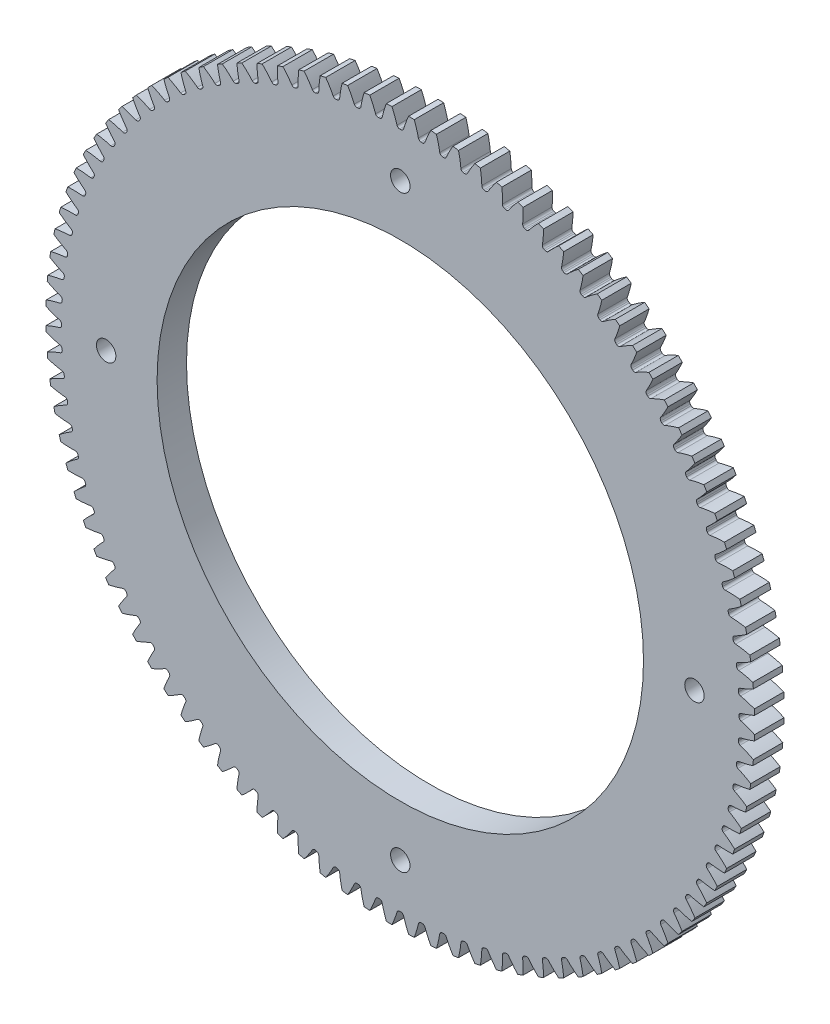
SolidWorks part; units mm, degrees
ref_plane "Front Plane" through (0, 0, 0) normal (0, 0, 1) x (1, 0, 0)
ref_plane "Top Plane" through (0, 0, 0) normal (0, 1, 0) x (1, 0, 0)
ref_plane "Right Plane" through (0, 0, 0) normal (1, 0, 0) x (0, 0, -1)
sketch "Sketch1" plane through (0, 0, 0) normal (0, 0, 1) x (1, 0, 0)
  line L0 (0, 0) -> (0, 75) construction
  line L1 (-24.1045, 83.7733) -> (24.1045, 66.2267) construction
  circle A0 centre (0, 0) radius 73.125 construction
  circle A1 centre (0, 0) radius 76.5 construction
  circle A2 centre (0, 0) radius 75 construction
  circle A3 centre (0, 0) radius 70.4769 construction
  circle A4 centre (0, 0) radius 40 construction
  circle A5 centre (0, 0) radius 7.5 construction
  point P8 (0.75, 0)
  point P13 (50, 0)
  dimension "OD" = 153
  dimension "Root Diameter" = 146.25
  dimension "Gear Pitch Diameter" = 150
  dimension "Base Diameter" = 140.9539
  dimension "Hub Diameter" = 80
  dimension "For Shaft Diameter" = 15
  dimension "Pressure Angle" = 20
  dimension "Number of Teeth" = 100
  dimension "Module" = 1.5
sketch "Sketch2" plane through (0, 0, 0) normal (1, 0, 0) x (0, 0, -1)
  line L0 (-14, 0) -> (6.35, 0) construction
  line L1 (6.35, 76.5) -> (6.35, -76.5) construction
  line L2 (0, -40) -> (-14, -40) construction
  line L3 (-14, 76.5) -> (6.35, 76.5) construction
  line L8 (-14, -40) -> (-14, 40) construction
  point P4 (0, 76.5)
  point P5 (-7, 0)
  dimension "Overall Width" = 20.35
  dimension "Hub Width" = 14
  dimension "Approx Set Screw Positon" = 7
  dimension "Face Width" = 6.35
sketch "Sketch3" plane through (0, 0, 0) normal (0, 0, 1) x (1, 0, 0)
  circle A0 centre (0, 0) radius 76.5
  circle A1 centre (0, 0) radius 76.5 construction
extrude "Boss-Extrude1" add sketch "Sketch3" against normal up to vertex (6.35 mm away) up to point (0, 0, -6.35)
sketch "Sketch4" plane through (0, 0, 0) normal (0, 0, 1) x (1, 0, 0)
  line L0 (73.1226, 0.589) -> (73.1226, -0.589)
  arc A3 (76.4789, 1.7978) -> (76.4789, -1.7978) centre (0, 0) cw
  circle A4 centre (0, 0) radius 76.5 construction
  arc A5 (73.1226, 0.589) -> (76.4789, 1.7978) centre (66.9977, 22.8603) ccw
  circle A8 centre (0, 0) radius 73.125 construction
  arc A9 (73.1226, -0.589) -> (76.4789, -1.7978) centre (66.9977, -22.8603) cw
  spline S0 degree 4 poles (70.4769, 0.0566) (70.4862, 0.0567) (70.5123, 0.0572) (70.5615, 0.0592) (70.6419, 0.0639) (70.7443, 0.072) (70.8767, 0.0848) (71.0327, 0.1031) (71.2042, 0.1265) (71.3909, 0.1556) (71.5772, 0.1877) (71.763, 0.2226) (71.9483, 0.2601) (72.1727, 0.3086) (72.4418, 0.3712) (72.7566, 0.4506) (73.1136, 0.5483) (73.4778, 0.6559) (73.8362, 0.7684) (74.1986, 0.8897) (74.5493, 1.0125) (74.9138, 1.148) (75.2504, 1.277) (75.6277, 1.4303) (75.9323, 1.5566) (76.3344, 1.7325) (76.572, 1.8392) (76.8501, 1.9673) (76.9736, 2.0258) (77.0497, 2.0619) knots 0 0 0 0 0 0.005377 0.015084 0.028532 0.04661 0.064855 0.092111 0.119476 0.146842 0.174209 0.201575 0.228941 0.256307 0.307035 0.361767 0.4165 0.471232 0.525964 0.580697 0.635429 0.690161 0.744894 0.799626 0.854358 0.909091 0.954545 1 1 1 1 1 construction
  spline S1 degree 4 poles (70.4769, 0.0566) (70.4862, 0.0567) (70.5123, 0.0572) (70.5615, 0.0592) (70.6419, 0.0639) (70.7443, 0.072) (70.8767, 0.0848) (71.0327, 0.1031) (71.2042, 0.1265) (71.3909, 0.1556) (71.5772, 0.1877) (71.763, 0.2226) (71.9483, 0.2601) (72.1727, 0.3086) (72.4418, 0.3712) (72.7566, 0.4506) (73.1136, 0.5483) (73.4778, 0.6559) (73.8362, 0.7684) (74.1986, 0.8897) (74.5493, 1.0125) (74.9138, 1.148) (75.2504, 1.277) (75.6277, 1.4303) (75.9323, 1.5566) (76.2472, 1.6943) (76.4005, 1.7625) (76.4789, 1.7978) knots 0 0 0 0 0 0.005377 0.015084 0.028532 0.04661 0.064855 0.092111 0.119476 0.146842 0.174209 0.201575 0.228941 0.256307 0.307035 0.361767 0.4165 0.471232 0.525964 0.580697 0.635429 0.690161 0.744894 0.799626 0.854358 0.909091 0.909091 0.909091 0.909091 0.909091 construction
  spline S2 degree 4 poles (70.4769, -0.0566) (70.4862, -0.0567) (70.5123, -0.0572) (70.5615, -0.0592) (70.6419, -0.0639) (70.7443, -0.072) (70.8767, -0.0848) (71.0327, -0.1031) (71.2042, -0.1265) (71.3909, -0.1556) (71.5772, -0.1877) (71.763, -0.2226) (71.9483, -0.2601) (72.1727, -0.3086) (72.4418, -0.3712) (72.7566, -0.4506) (73.1136, -0.5483) (73.4778, -0.6559) (73.8362, -0.7684) (74.1986, -0.8897) (74.5493, -1.0125) (74.9138, -1.148) (75.2504, -1.277) (75.6277, -1.4303) (75.9323, -1.5566) (76.3344, -1.7325) (76.572, -1.8392) (76.8501, -1.9673) (76.9736, -2.0258) (77.0497, -2.0619) knots 0 0 0 0 0 0.005377 0.015084 0.028532 0.04661 0.064855 0.092111 0.119476 0.146842 0.174209 0.201575 0.228941 0.256307 0.307035 0.361767 0.4165 0.471232 0.525964 0.580697 0.635429 0.690161 0.744894 0.799626 0.854358 0.909091 0.954545 1 1 1 1 1 construction
  spline S3 degree 4 poles (70.4769, -0.0566) (70.4862, -0.0567) (70.5123, -0.0572) (70.5615, -0.0592) (70.6419, -0.0639) (70.7443, -0.072) (70.8767, -0.0848) (71.0327, -0.1031) (71.2042, -0.1265) (71.3909, -0.1556) (71.5772, -0.1877) (71.763, -0.2226) (71.9483, -0.2601) (72.1727, -0.3086) (72.4418, -0.3712) (72.7566, -0.4506) (73.1136, -0.5483) (73.4778, -0.6559) (73.8362, -0.7684) (74.1986, -0.8897) (74.5493, -1.0125) (74.9138, -1.148) (75.2504, -1.277) (75.6277, -1.4303) (75.9323, -1.5566) (76.2472, -1.6943) (76.4005, -1.7625) (76.4789, -1.7978) knots 0 0 0 0 0 0.005377 0.015084 0.028532 0.04661 0.064855 0.092111 0.119476 0.146842 0.174209 0.201575 0.228941 0.256307 0.307035 0.361767 0.4165 0.471232 0.525964 0.580697 0.635429 0.690161 0.744894 0.799626 0.854358 0.909091 0.909091 0.909091 0.909091 0.909091 construction
  dimension "D1" = 1.1781
extrude "Cut-Extrude1" cut sketch "Sketch4" against normal through all both and the other way through all
fillet "Fillet1" radius 0.589 2 edges at (73.1226, 0.589, -3.175) (73.1226, -0.589, -3.175)
pattern_circular "CirPattern1" count 100 over 360 about axis through (0, 0, 14) along (0, 0, -1) of "Cut-Extrude1", "Fillet1"
sketch "Sketch5" plane through (0, 0, -6.35) normal (0, 0, -1) x (-1, 0, 0)
  circle A0 centre (0, 0) radius 52.5
  dimension "D1" = 105
extrude "Cut-Extrude2" cut sketch "Sketch5" against normal through all
sketch "Sketch6" plane through (0, 0, -6.35) normal (0, 0, -1) x (-1, 0, 0)
  circle A0 centre (63.5, 0) radius 2.1
  circle A1 centre (0, -63.5) radius 2.1
  circle A2 centre (-63.5, 0) radius 2.1
  circle A3 centre (0, 63.5) radius 2.1
  point P11 (0, 0)
  dimension "D1" = 4.2
  dimension "D3" = 127
  dimension "D2" = 4
extrude "Cut-Extrude3" cut sketch "Sketch6" against normal through all
sketch "Sketch7" plane through (0, 0, 0) normal (0, 0, 1) x (1, 0, 0)
  circle A0 centre (0, 0) radius 75 construction
  dimension "D1" = 150
sketch "Sketch8" plane through (0, 0, 0) normal (0, 1, 0) x (1, 0, 0)
  line L0 (0, 0) -> (0, 8.1709) construction
  line L1 (-75, 0) -> (75, 0) construction
equation "\"Number of Teeth\"= 100"
equation "\"Module\"= 1.5"
equation "\"Diametral Pitch\"= 1 / \"Module\""
equation "\"Dedendum\"= 1.25 / \"Diametral Pitch\""
equation "\"Pitch Diameter\"= \"Module\" * \"Number of Teeth\""
equation "\"Root Diameter\"= \"Pitch Diameter\" - ( 2 * \"Dedendum\" )"
equation "\"Root Diameter@Sketch1\"=\"Root Diameter\""
equation "\"OD@Sketch1\" = \"Outside Diameter\""
equation "\"D1@CirPattern1\"=\"Number of Teeth\""
equation "\"Pressure Angle\"=20"
equation "\"Base Diameter\"= \"Pitch Diameter\" * cos ( \"Pressure Angle\" )"
equation "\"Outside Diameter\"= ( \"Number of Teeth\" + 2 ) / \"Diametral Pitch\""
equation "\"Pitch Angle\"= 360deg / \"Number of Teeth\""
equation "\"Alpha\"= sqr ( \"Pitch Diameter\" ^ 2 - \"Base Diameter\" ^ 2 ) / \"Base Diameter\" * 180 / PI - \"Pressure Angle\""
equation "\"Beta\"= ( \"Pitch Angle\" / 4 - \"Alpha\" )"
equation "\"Phi\"= sqr ( ( \"Outside Diameter\" / 2 ) ^ 2 - ( \"Base Diameter\" / 2 ) ^ 2 ) / ( \"Base Diameter\" / 2 )"
equation "\"Addendum\"= 1 / \"Diametral Pitch\""
equation "\"WorkingDepth\"= 2 / \"Diametral Pitch\""
equation "\"WholeDepth\"= 2.25 / \"Diametral Pitch\""
equation "\"Clearance\"= 0.25 / \"Diametral Pitch\""
equation "\"ToothThickness\"= ( pi * 2 ) / \"Diametral Pitch\""
equation "\"CircularPitch\"= pi / \"Diametral Pitch\""
equation "\"Number of Teeth@Sketch1\"=\"Number of Teeth\""
equation "\"Module@Sketch1\"=\"Module\""
equation "\"Pressure Angle@Sketch1\"=\"Pressure Angle\""
equation "\"Gear Pitch Diameter@Sketch1\"=\"Pitch Diameter\""
equation "\"Base Diameter@Sketch1\"=\"Base Diameter\""
equation "\"Fillet\"= \"Clearance\" * cos ( \"Pressure Angle\" ) * tan ( ( 90 + \"Pressure Angle\" ) / 2 )"
equation "\"D1\"= \"Fillet\""
equation "\"Approx Set Screw Positon@Sketch2\" = \"Hub Width@Sketch2\" / 2"
equation "\"D2\"= \"Fillet\" * 2"
equation "\"D1@Sketch4\"=\"CircularPitch\"*0.25"
equation "\"D1@Fillet1\"=\"CircularPitch\"*0.125"
equation "\"Overall Width@Sketch2\"=14+0.25in"
equation "\"D3@Sketch6\"=5in"
